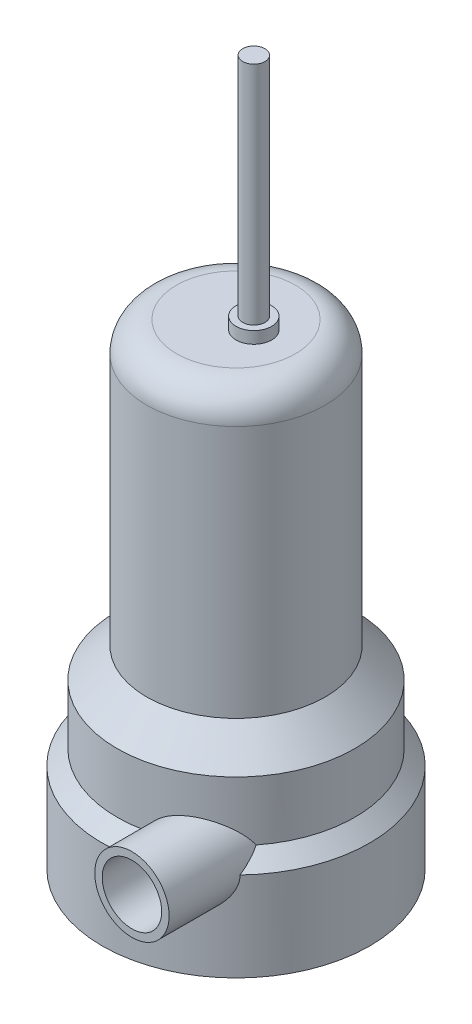
SolidWorks part; units mm, degrees
ref_plane "Front" through (0, 0, 0) normal (0, 0, 1) x (1, 0, 0)
ref_plane "Top" through (0, 0, 0) normal (0, 1, 0) x (1, 0, 0)
ref_plane "Right" through (0, 0, 0) normal (1, 0, 0) x (0, 0, -1)
sketch "Sketch1" plane through (0, 0, 0) normal (0, 0, 1) x (1, 0, 0)
  line L0 (0, 0) -> (-57.15, 0)
  line L1 (-57.15, 0) -> (-57.15, 38.1)
  line L2 (-57.15, 38.1) -> (-50.8, 38.1)
  line L3 (-50.8, 38.1) -> (-50.8, 69.85)
  line L4 (-50.8, 69.85) -> (-38.1, 69.85)
  line L5 (-38.1, 69.85) -> (-38.1, 190.5)
  line L6 (-25.4, 203.2) -> (0, 203.2)
  line L7 (0, 203.2) -> (0, 0)
  arc A0 (-25.4, 203.2) -> (-38.1, 190.5) centre (-25.4, 190.5) ccw
  dimension "D7" = 12.7
  dimension "D1" = 57.15
  dimension "D2" = 203.2
  dimension "D3" = 38.1
  dimension "D4" = 50.8
  dimension "D5" = 38.1
  dimension "D6" = 31.75
revolve "Revolve1" add sketch "Sketch1" angle 360 about L7
chamfer "Chamfer1" distance 6.35 angle 45 1 edges at (-50.8, 38.1, 0)
chamfer "Chamfer2" distance 12.7 angle 45 1 edges at (-38.1, 69.85, 0)
sketch "Sketch2" plane through (0, 203.2, 0) normal (0, 1, 0) x (1, 0, 0)
  line L0 (0, 0) -> (7.62, 0) construction
  circle A0 centre (7.62, 0) radius 4.7625
  dimension "D2" = 9.525
  dimension "D1" = 7.62
extrude "Boss-Extrude1" add sketch "Sketch2" along normal blind 101.6 separate body
sketch "Sketch3" plane through (0, 0, 0) normal (0, 0, 1) x (1, 0, 0)
  line L3 (-57.15, 0) -> (57.15, 0) construction
  circle A0 centre (25.4, 38.1) radius 12.7
  circle A1 centre (25.4, 38.1) radius 15.875
  dimension "D1" = 25.4
  dimension "D2" = 25.4
  dimension "D4" = 31.75
  dimension "D3" = 31.75
extrude "Boss-Extrude2" add sketch "Sketch3" along normal blind 69.85
sketch "Sketch4" plane through (0, 0, 69.85) normal (0, 0, 1) x (1, 0, 0)
  circle A0 centre (25.4, 38.1) radius 12.7 construction
  circle A1 centre (25.4, 38.1) radius 12.7
extrude "Cut-Extrude1" cut sketch "Sketch4" against normal blind 69.85
sketch "Sketch5" plane through (0, 203.2, 0) normal (0, 1, 0) x (1, 0, 0)
  circle A0 centre (7.62, 0) radius 7.62
  dimension "D1" = 15.24
extrude "Boss-Extrude3" add sketch "Sketch5" along normal blind 5.08
ref_axis "Axis1" [suppressed] through (25.4, 38.1, 69.85) along (0, 0, -1)
ref_plane "Plane1" [suppressed] through (25.4, 0, 0) normal (1, 0, 0) x (0, 0, -1)
sketch "Sketch6" [suppressed] plane through (25.4, 0, 0) normal (1, 0, 0) x (0, 0, -1)
  line L0 (-69.85, 38.1) -> (-349.25, 38.1)
  line L1 (-69.85, 53.975) -> (-69.85, 22.225) construction
  line L2 (-374.65, 63.5) -> (-374.65, 3771.9)
  line L3 (-400.05, 3797.3) -> (-730.25, 3797.3)
  arc A0 (-374.65, 63.5) -> (-349.25, 38.1) centre (-349.25, 63.5) ccw
  arc A1 (-374.65, 3771.9) -> (-400.05, 3797.3) centre (-400.05, 3771.9) ccw
  point P8 (-374.65, 38.1)
  point P11 (-374.65, 3797.3)
  dimension "D4" = 25.4
  dimension "D1" = 304.8
  dimension "D2" = 3759.2
  dimension "D3" = 355.6
ref_plane "Plane3" [suppressed] through (0, 3797.3, 0) normal (0, 1, 0) x (1, 0, 0)
sketch "Sketch8" [suppressed] plane through (0, 3797.3, 0) normal (0, 1, 0) x (1, 0, 0)
  line L0 (25.4, -400.05) -> (25.4, -730.25) construction
  line L1 (50.8, -755.65) -> (7594.6, -755.65)
  arc A0 (25.4, -730.25) -> (50.8, -755.65) centre (50.8, -730.25) ccw
  dimension "D1" = 25.4
  dimension "D2" = 7569.2
ref_plane "Plane4" [suppressed] through (0, 0, 755.65) normal (0, 0, 1) x (1, 0, 0)
sketch "Sketch9" [suppressed] plane through (0, 0, 755.65) normal (0, 0, 1) x (1, 0, 0)
  line L0 (7620, 3771.9) -> (7620, 38.1)
  line L1 (50.8, 3797.3) -> (7594.6, 3797.3) construction
  arc A0 (7594.6, 3797.3) -> (7620, 3771.9) centre (7594.6, 3771.9) cw
  dimension "D1" = 25.4
  dimension "D2" = 3733.8
ref_plane "Plane5" [suppressed] through (7620, 0, 0) normal (1, 0, 0) x (0, 0, -1)
sketch "Sketch11" [suppressed] plane through (7620, 0, 0) normal (1, 0, 0) x (0, 0, -1)
  line L0 (-755.65, 3771.9) -> (-755.65, 38.1) construction
  line L1 (-730.25, 12.7) -> (-501.65, 12.7)
  arc A0 (-755.65, 38.1) -> (-730.25, 12.7) centre (-730.25, 38.1) ccw
  dimension "D1" = 25.4
  dimension "D2" = 254
curve "CompCurve1" [suppressed]
sketch "Sketch10" plane through (0, 0, 69.85) normal (0, 0, 1) x (1, 0, 0)
  line L0 (25.4, 48.26) -> (25.4, 50.8) construction
  circle A0 centre (25.4, 38.1) radius 12.7 construction
  circle A1 centre (25.4, 38.1) radius 12.7
  circle A2 centre (25.4, 38.1) radius 10.16
  dimension "D1" = 2.54
sweep "Sweep1" [suppressed] add profiles "Sketch10" path "CompCurve1"
